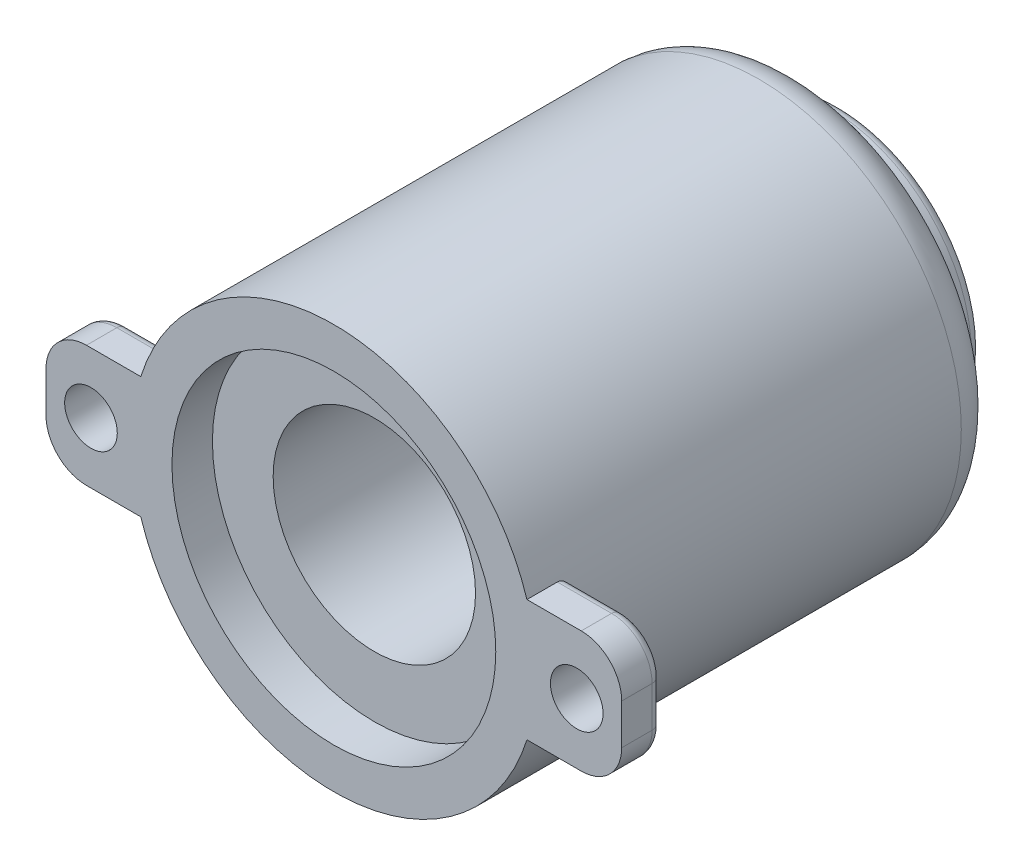
SolidWorks part; units mm, degrees
ref_plane "Front Plane" through (0, 0, 0) normal (0, 0, 1) x (1, 0, 0)
ref_plane "Top Plane" through (0, 0, 0) normal (0, 1, 0) x (1, 0, 0)
ref_plane "Right Plane" through (0, 0, 0) normal (1, 0, 0) x (0, 0, -1)
sketch "Sketch1" plane through (0, 0, 0) normal (0, 0, 1) x (1, 0, 0)
  line L0 (16.4093, 0) -> (-14.6473, 0) construction
  line L1 (0, 13.7662) -> (0, -15.7486)
  circle A0 centre (0, 0) radius 10
  circle A1 centre (0, 0) radius 5
  circle A2 centre (0, 0) radius 7
  dimension "D1" = 20
  dimension "D2" = 10
  dimension "D3" = 14
extrude "Boss-Extrude1" add sketch "Sketch1" along normal blind 25 contours A0
extrude "Cut-Extrude2" cut sketch "Sketch1<3>" against normal blind 25 and the other way through all contours L0 A1 L1 | L0 L1 A1 | L1 L0 A1 | A1 L0 L1 region at (2.1221, -2.1221, 0) region at (2.1221, 2.1221, 0) region at (-2.1221, -2.1221, 0) region at (-2.1221, 2.1221, 0)
sketch "Sketch1<3>" plane through (0, 0, 0) normal (0, 0, 1) x (1, 0, 0) same geometry as "Sketch1"
extrude "Cut-Extrude3" cut sketch "Sketch1<7>" along normal blind 2 contours L0 A0 L1 A2 | L0 A2 L1 A0 | A2 L0 A0 L1 | A0 L0 A2 L1 region at (5.4674, -5.4674, 0) region at (5.4674, 5.4674, 0) region at (-5.4674, 5.4674, 0) region at (-5.4674, -5.4674, 0)
sketch "Sketch1<7>" plane through (0, 0, 0) normal (0, 0, 1) x (1, 0, 0) same geometry as "Sketch1"
sketch "Sketch5" plane through (0, 0, 25) normal (0, 0, 1) x (1, 0, 0)
  circle A0 centre (0, 0) radius 8
extrude "Cut-Extrude4" cut sketch "Sketch5" against normal blind 2
sketch "Sketch6" plane through (0, 0, 25) normal (0, 0, 1) x (1, 0, 0)
  line L0 (-14.2225, 0) -> (14.1572, 0) construction
  line L1 (-14.2225, -1) -> (-14.2225, 1)
  line L2 (-12.2225, 3) -> (-9.5394, 3)
  line L3 (-12.2225, -3) -> (-9.5394, -3)
  line L4 (0, 1.1242) -> (0, -1.1847) construction
  line L5 (12.2225, -3) -> (9.5394, -3)
  line L6 (14.2225, -1) -> (14.2225, 1)
  line L7 (12.2225, 3) -> (9.5394, 3)
  circle A0 centre (0, 0) radius 10 construction
  arc A1 (-12.2225, 3) -> (-14.2225, 1) centre (-12.2225, 1) ccw
  arc A2 (-12.2225, -3) -> (-14.2225, -1) centre (-12.2225, -1) cw
  arc A3 (12.2225, -3) -> (14.2225, -1) centre (12.2225, -1) ccw
  arc A4 (12.2225, 3) -> (14.2225, 1) centre (12.2225, 1) cw
  circle A5 centre (-12, 0) radius 1.3
  circle A6 centre (12, 0) radius 1.3
  point P9 (-14.2225, 3)
  circle M7 centre (0, 0) radius 10
  dimension "D2" = 2
  dimension "D3" = 2.6
  dimension "D1" = 3
  dimension "D4" = 12
extrude "Boss-Extrude2" add sketch "Sketch6" against normal blind 2 contours A2 L3 L2 A1 L1 A5 M7 | A4 L7 L5 A3 L6 A6 M7 region at (-14.1464, 0, 25) region at (9.9594, -1.5291, 25)
fillet "Fillet1" radius 2 1 edges at (10, 0, 2)
fillet "Fillet2" radius 0.5 12 edges at (10.8809, -3, 23) (13.6367, -2.4142, 23) (10.8809, 3, 23) (13.6367, 2.4142, 23) (-10.8809, -3, 23) (-13.6367, -2.4142, 23) (-14.2225, 0, 23) (-13.6367, 2.4142, 23) (7, 0, 0) (7, 0, 2) (14.2225, 0, 23) (-10.8809, 3, 23)
